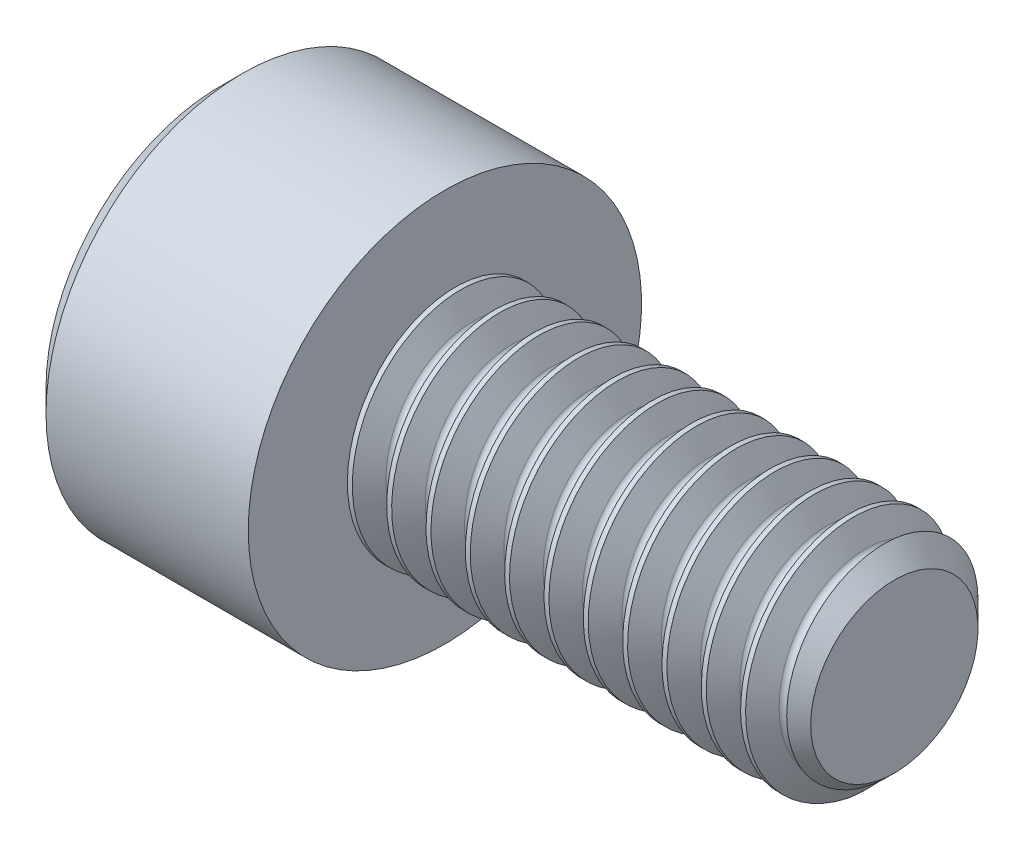
SolidWorks part; units mm, degrees
material "AISI Type 316L stainless steel"
ref_plane "Front Plane" through (0, 0, 0) normal (0, 0, 1) x (1, 0, 0)
ref_plane "Top Plane" through (0, 0, 0) normal (0, 1, 0) x (1, 0, 0)
ref_plane "Right Plane" through (0, 0, 0) normal (1, 0, 0) x (0, 0, -1)
sketch "Sketch1" plane through (0, 0, 0) normal (0, 0, 1) x (1, 0, 0)
  line L0 (-88.7055, 0) -> (96.9812, 0) construction
  line L1 (0, 0) -> (0, 3.5)
  line L2 (0, 3.5) -> (4, 3.5)
  line L4 (12, 0) -> (12, 1.989)
  line L5 (12, 1.989) -> (4, 1.989)
  line L6 (4, 1.989) -> (4, 3.5)
  line L7 (0, 0) -> (12, 0)
revolve "Revolve1" add sketch "Sketch1" angle 360 about L0
chamfer "Chamfer1" distance 0.5 angle 45 1 edges at (12, 0, 1.989)
chamfer "Chamfer2" distance 0.4 angle 45 1 edges at (0, 0, 3.5)
sketch "Sketch3" plane through (0, 0, 0) normal (1, 0, 0) x (0, 0, -1)
  line L1 (-1.7321, 0) -> (-0.866, -1.5)
  line L2 (-0.866, -1.5) -> (0.866, -1.5)
  line L3 (0.866, -1.5) -> (1.7321, 0)
  line L4 (1.7321, 0) -> (0.866, 1.5)
  line L5 (0.866, 1.5) -> (-0.866, 1.5)
  line L6 (-0.866, 1.5) -> (-1.7321, 0)
  circle A0 centre (0, 0) radius 1.5 construction
extrude "Cut-Extrude1" cut sketch "Sketch3" along normal blind 2
chamfer "Chamfer3" distance 0.3 angle 45 6 edges at (0, 1.5, 0) (0, 0.75, 1.299) (0, -0.75, 1.299) (0, -1.5, 0) (0, -0.75, -1.299) (0, 0.75, -1.299)
sketch "Sketch5" plane through (12, 0, 0) normal (1, 0, 0) x (0, 0, -1)
  circle A0 centre (0, 0) radius 1.989
curve "Helix/Spiral1" pitch 0.7 height 8 radius 1.989 centre (12, 0, 0) axis (-1, 0, 0) start towards (0, 0, -1)
sketch "Sketch8" plane through (0, 0, 0) normal (0, 1, 0) x (1, 0, 0)
  line L0 (12, 1.989) -> (12, 1.4588) construction
  line L1 (12.0875, 1.6102) -> (12.4592, 2.2541)
  line L2 (12.4592, 2.2541) -> (11.5408, 2.2541)
  line L3 (11.5408, 2.2541) -> (11.9125, 1.6102)
  line L4 (12, -1.489) -> (12, 1.489) construction
  circle A0 centre (12, 1.989) radius 0.2651 construction
  arc A1 (12.0875, 1.6102) -> (11.9125, 1.6102) centre (12, 1.6607) cw
  dimension "D2" = 0.101
  dimension "D1" = 0.5302
sweep "Cut-Sweep1" cut profiles "Sketch8" path "Helix/Spiral1" align with end faces yes
